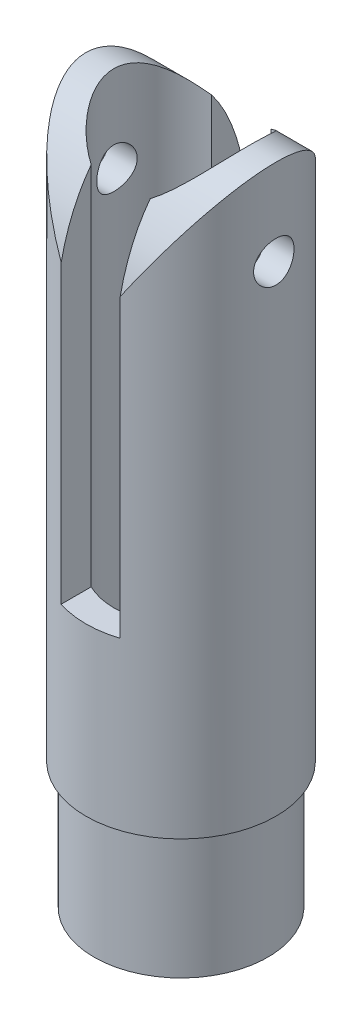
SolidWorks part; units mm, degrees
material "Commercially Pure titanium (Ti-55)  UNS R50550*"
ref_plane "Front Plane" through (0, 0, 0) normal (0, 0, 1) x (1, 0, 0)
ref_plane "Top Plane" through (0, 0, 0) normal (0, 1, 0) x (1, 0, 0)
ref_plane "Right Plane" through (0, 0, 0) normal (1, 0, 0) x (0, 0, -1)
sketch "Sketch1" plane through (0, 0, 0) normal (0, 1, 0) x (1, 0, 0)
  circle A0 centre (0, 0) radius 2.15
  dimension "D1" = 4.3
extrude "Boss-Extrude1" add sketch "Sketch1" along normal blind 3.12
sketch "Sketch2" plane through (0, 3.12, 0) normal (0, 1, 0) x (1, 0, 0)
  circle A0 centre (0, 0) radius 2.35
  dimension "D1" = 4.7
extrude "Boss-Extrude2" add sketch "Sketch2" along normal blind 14.2
shell "Shell1" thickness 0.69 removed face at (0, 17.32, 2.35) removed face at (0, 0, 2.15)
sketch "Sketch7" plane through (0, 0, 0) normal (1, 0, 0) x (0, 0, -1)
  line L1 (-2.35, 17.32) -> (-2.35, 3.12) construction
  line L2 (-2.35, 13.4) -> (2.35, 13.4) construction
  line L3 (2.35, 3.12) -> (2.35, 17.32) construction
  line L6 (-4.35, 13.4) -> (-2.35, 13.4)
  line L7 (2.35, 13.4) -> (4.35, 13.4)
  ellipse E0 centre (0, 13.4) end of major axis (0, 17.1335) minor radius 2.35 (2.35, 13.4) -> (-2.35, 13.4) ccw
  spline S1 degree 3 poles (4.35, 13.4) (4.35, 14.0654) (4.1923, 15.4127) (3.4748, 17.2502) (2.3882, 18.5315) (1.115, 19.1944) (0, 19.3828) (-1.115, 19.1944) (-2.3882, 18.5315) (-3.4748, 17.2502) (-4.1923, 15.4127) (-4.35, 14.0654) (-4.35, 13.4) knots -1.570796 -1.570796 -1.570796 -1.570796 -1.178097 -0.785398 -0.392699 -0.19635 0 0.19635 0.392699 0.785398 1.178097 1.570796 1.570796 1.570796 1.570796
  dimension "D1" = 4.35
  dimension "D3" = 13.4
  dimension "D2" = 9.6665
extrude "Cut-Extrude2" cut sketch "Sketch7" against normal blind 10 and the other way blind 10
ref_plane "Plane1" through (0, 17.32, 0) normal (0, -1, 0) x (-1, 0, 0)
sketch "Sketch9" plane through (0, 17.32, 0) normal (0, -1, 0) x (-1, 0, 0)
  line L0 (0, 0) -> (0, 2.3639) construction
  line L1 (0, 2.3639) -> (-0.73, 2.3639) construction
  line L2 (0, 0) -> (0, -2.3647) construction
  line L7 (0, -2.3647) -> (0.73, -2.3647) construction
  line L13 (0.73, -2.3647) -> (-0.73, -2.3647)
  line L14 (0.73, -2.3647) -> (0.73, 2.3639)
  line L15 (0.73, 2.3639) -> (-0.73, 2.3639)
  line L16 (-0.73, -2.3647) -> (-0.73, 2.3639)
  dimension "D1" = 0.73
  dimension "D2" = 0.73
  dimension "D3" = 4.7286
  dimension "D4" = 2.3647
extrude "Cut-Extrude3" cut sketch "Sketch9" along normal blind 10.08
sketch "Sketch11" plane through (0, 0, 0) normal (1, 0, 0) x (0, 0, -1)
  line L0 (0, 0) -> (0, 15) construction
  line L1 (-2.15, 0) -> (2.15, 0) construction
  circle A0 centre (0, 15) radius 0.5
  dimension "D2" = 1
  dimension "D1" = 15
extrude "Cut-Extrude4" cut sketch "Sketch11" against normal blind 10.08 and the other way blind 10.08
